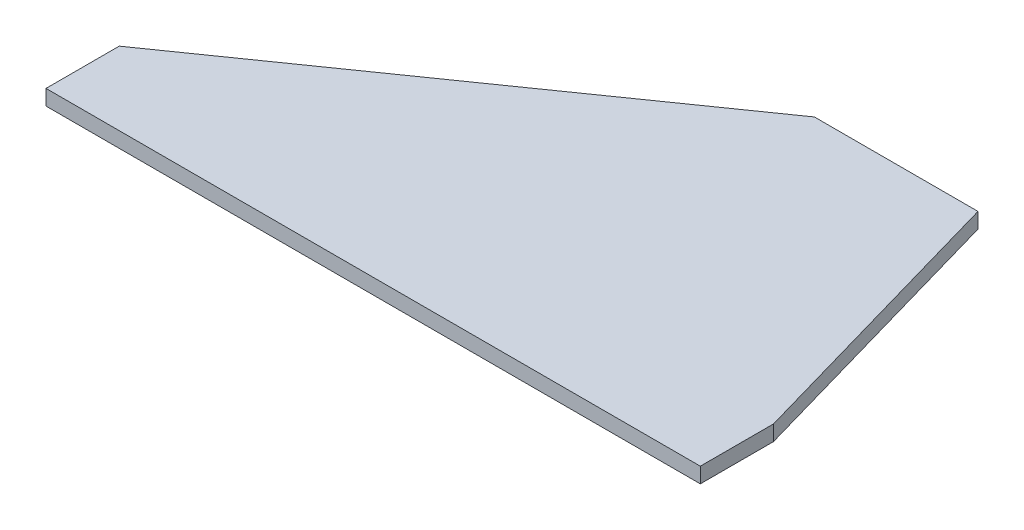
SolidWorks part; units mm, degrees
ref_plane "Front Plane" through (0, 0, 0) normal (0, 0, 1) x (1, 0, 0)
ref_plane "Top Plane" through (0, 0, 0) normal (0, 1, 0) x (1, 0, 0)
ref_plane "Right Plane" through (0, 0, 0) normal (1, 0, 0) x (0, 0, -1)
sketch "Sketch1" plane through (0, 0, 0) normal (0, 1, 0) x (1, 0, 0)
  line L0 (0, 0) -> (0, 22.733)
  line L1 (0, 22.733) -> (127, 111.633)
  line L2 (127, 111.633) -> (177.8, 111.633)
  line L3 (177.8, 111.633) -> (203.2, 22.733)
  line L4 (203.2, 22.733) -> (203.2, 0)
  line L5 (203.2, 0) -> (0, 0)
  line L6 (0, 22.733) -> (0, 111.633) construction
  line L7 (0, 111.633) -> (127, 111.633) construction
  dimension "D1" = 203.2
  dimension "D2" = 22.733
  dimension "D3" = 50.8
  dimension "D4" = 88.9
  dimension "D5" = 127
extrude "Boss-Extrude1" add sketch "Sketch1" along normal blind 2.3813 and the other way blind 2.3813 contours L3 L4 L5 L0 L1 L2
equation "\"Root Chord\"= 8"
equation "\"Tip Chord\"=2"
equation "\"Height\" = 3.5"
equation "\"Sweep Length\"=5"
equation "\"Fin Thickness\"= 3 / 16"
equation "\"Bevel Depth\"= 1 / 16"
equation "\"Bevel Width\"= 1 / 4"
equation "\"Tab Height\"=0.895"
equation "\"D2@Sketch1\"=\"Tab Height\""
equation "\"D4@Sketch1\"=\"Height\""
equation "\"D5@Sketch1\"=\"Sweep Length\""
equation "\"D3@Sketch1\"=\"Tip Chord\""
equation "\"D1@Sketch1\"=\"Root Chord\""
equation "\"D1@Boss-Extrude1\"=\"Fin Thickness\"/2"
equation "\"D2@Boss-Extrude1\"=\"Fin Thickness\"/2"
equation "\"D1@Chamfer2\"=\"Bevel Depth\""
equation "\"D3@Chamfer2\"=\"Bevel Width\""
